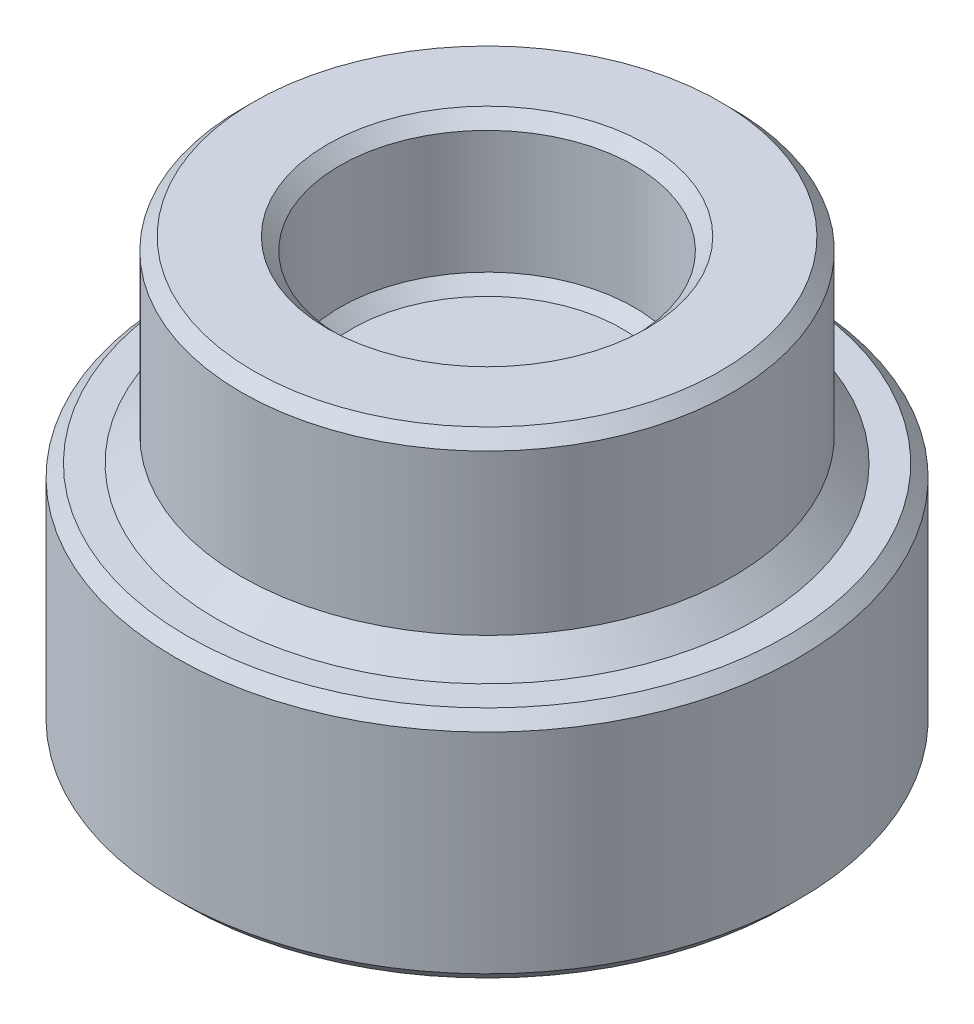
SolidWorks part; units mm, degrees
note: '?' marks a value the reader was unsure of. The reader was unsure of these and kept them because the rebuilt part matched: shared geometry of "Sketch1<3>".
material "ABS"
ref_plane "Front Plane" through (0, 0, 0) normal (0, 0, 1) x (1, 0, 0)
ref_plane "Top Plane" through (0, 0, 0) normal (0, 1, 0) x (1, 0, 0)
ref_plane "Right Plane" through (0, 0, 0) normal (1, 0, 0) x (0, 0, -1)
ref_axis "X Axis" through (88.99, 0, 0) along (-1, 0, 0)?
ref_axis "Y Axis" through (0, 55, 0) along (0, -1, 0)?
ref_axis "Z Axis" through (0, 0, -88.99) along (0, 0, 1)?
sketch "Sketch1" plane through (0, 0, 0) normal (0, 1, 0) x (1, 0, 0)
  circle A0 centre (0, 0) radius 5
  circle A1 centre (0, 0) radius 3
  dimension "D1" = 6
  dimension "D2" = 10
extrude "Boss-Extrude1" add sketch "Sketch1" along normal blind 1 contours A1 | A0 A1
extrude "Boss-Extrude2" add sketch "Sketch1<3>" along normal blind 4
sketch "Sketch1<3>" plane through (0, 0, 0) normal (0, 1, 0) x (1, 0, 0) same geometry as "Sketch1"
chamfer "Chamfer1" distance 0.25 angle 45 3 edges at (0, 4, 3) (0, 4, 5) (0, 1, 3)
sketch "Sketch5" plane through (0, 0, 0) normal (0, 1, 0) x (1, 0, 0)
  circle A0 centre (0, 0) radius 6.35
  dimension "D1" = 12.7
extrude "Boss-Extrude4" add sketch "Sketch5" against normal blind 4.7625
sketch "Sketch4" plane through (0, -4.7625, 0) normal (0, -1, 0) x (-1, 0, 0)
  point P0 (0, 0)
hole_wizard "3/8 (0.375) Diameter Hole1" [suppressed] positions "Sketch4" profile "Sketch3" hole size "3/8" standard "ANSI Inch"
sketch "Sketch3" plane through (0, -12.5, 0) normal (1, 0, 0) x (0, 0, -1)
  line L0 (0, 0) -> (0, 12.5)
  line L1 (0, 12.5) -> (4.7625, 12.0833)
  line L2 (4.7625, 12.0833) -> (4.7625, 0.635)
  line L3 (4.7625, 0.635) -> (5.3975, 0)
  line L5 (5.3975, 0) -> (0, 0)
  line L6 (-4.7625, 0.635) -> (-5.3975, 0) construction
  line L10 (0, 12.5) -> (-4.7625, 12.0833) construction
  line L11 (0, -6.35) -> (0, 107.95) construction
  dimension "Hole Dia." = 9.525
  dimension "Hole Depth" = 12.5
  dimension "Near C'Sink Dia." = 10.795
  dimension "Near C'Sink Angle" = 90
  dimension "Drill Angle" = 170
sketch "Sketch8" plane through (0, -4.7625, 0) normal (0, -1, 0) x (-1, 0, 0)
  point P0 (0, 0)
hole_wizard "#2 (0.221) Diameter Hole1" [suppressed] positions "Sketch8" profile "Sketch7" hole size "#2" standard "ANSI Inch"
sketch "Sketch7" plane through (0, -4.7625, 0) normal (1, 0, 0) x (0, 0, -1)
  line L0 (0, 0) -> (0, 4.76)
  line L1 (0, 4.76) -> (2.8067, 4.2651)
  line L2 (2.8067, 4.2651) -> (2.8067, 0.635)
  line L3 (2.8067, 0.635) -> (3.4417, 0)
  line L5 (3.4417, 0) -> (0, 0)
  line L6 (-2.8067, 0.635) -> (-3.4417, 0) construction
  line L10 (0, 4.76) -> (-2.8067, 4.2651) construction
  line L11 (0, -6.35) -> (0, 107.95) construction
  dimension "Hole Dia." = 5.6134
  dimension "Hole Depth" = 4.76
  dimension "Near C'Sink Dia." = 6.8834
  dimension "Near C'Sink Angle" = 90
  dimension "Drill Angle" = 160
sketch "Sketch11" plane through (0, -4.7625, 0) normal (0, -1, 0) x (-1, 0, 0)
  point P0 (0, 0)
hole_wizard "5/16 (0.3125) Diameter Hole1" positions "Sketch11" profile "Sketch10" hole size "5/16" standard "ANSI Inch"
sketch "Sketch10" plane through (0, -4.7625, 0) normal (1, 0, 0) x (0, 0, -1)
  line L0 (0, 0) -> (0, 4.7625)
  line L1 (0, 4.7625) -> (3.9687, 4.4153)
  line L2 (3.9687, 4.4153) -> (3.9688, 0.127)
  line L3 (3.9688, 0.127) -> (4.0957, 0)
  line L5 (4.0957, 0) -> (0, 0)
  line L6 (-3.9688, 0.127) -> (-4.0957, 0) construction
  line L10 (0, 4.7625) -> (-3.9688, 4.4153) construction
  line L11 (0, -6.35) -> (0, 107.95) construction
  dimension "Hole Dia." = 7.9375
  dimension "Hole Depth" = 4.7625
  dimension "Near C'Sink Dia." = 8.1915
  dimension "Near C'Sink Angle" = 90
  dimension "Drill Angle" = 170
chamfer "Chamfer2" distance 0.25 angle 45 2 edges at (0, -4.7625, 6.35) (0, 0, 6.35)
chamfer "Chamfer3" distance 0.5 angle 45 1 edges at (0, 0, 5)
